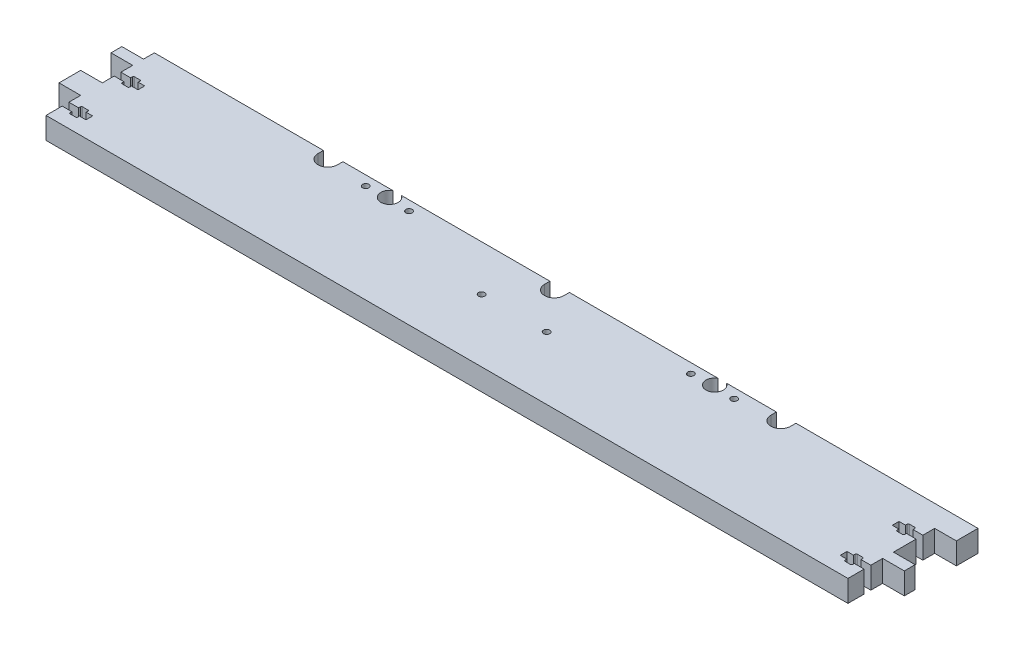
SolidWorks part; units mm, degrees
ref_plane "Front Plane" through (0, 0, 0) normal (0, 0, 1) x (1, 0, 0)
ref_plane "Top Plane" through (0, 0, 0) normal (0, 1, 0) x (1, 0, 0)
ref_plane "Right Plane" through (0, 0, 0) normal (1, 0, 0) x (0, 0, -1)
sketch "Sketch1" plane through (0, 0, 0) normal (0, 1, 0) x (1, 0, 0)
  line L0 (0, 25) -> (0, -25)
  line L1 (-185, 25) -> (0, 25)
  line L2 (-185, 25) -> (-185, -25) construction
  line L3 (-185, -25) -> (0, -25)
  line L4 (-185, -4) -> (-195, -4) construction
  line L5 (-185, 25) -> (0, 0) construction
  line L6 (-185, -25) -> (0, 0) construction
  line L7 (-185, -9) -> (-195, -9)
  line L8 (-195, -9) -> (-195, 1)
  line L9 (-195, 1) -> (-185, 1)
  line L10 (-185, 1) -> (-185, 25)
  line L11 (-185, -9) -> (-185, -25)
  line L47 (0, -25) -> (0, 25) construction
  line L89 (0, -25) -> (0, 25) construction
  point P0 (0, 0)
  dimension "D1" = 185
  dimension "D25" = 25
  dimension "D4" = 50
  dimension "D3" = 21
  dimension "D5" = 10
  dimension "D6" = 10
  dimension "D7" = 5
extrude "MainBody" add sketch "Sketch1" along normal blind 10 contours L3 region at (-93.5428, 0, 0.0428)
sketch "Sketch5" plane through (0, 10, 0) normal (0, 1, 0) x (1, 0, 0)
  line L0 (-185, 8) -> (-174, 8) construction
  line L1 (-185, 1) -> (-185, 25) construction
  line L2 (-185, 9.55) -> (-174, 9.55) construction
  line L3 (-174, 9.55) -> (-174, 6.45) construction
  line L4 (-174, 6.45) -> (-185, 6.45) construction
  line L5 (-185, 9.55) -> (-180.5, 9.55)
  line L6 (-180.5, 9.55) -> (-180.5, 10.35)
  line L7 (-180, 10.85) -> (-177.5, 10.85)
  line L8 (-177, 10.35) -> (-177, 9.55)
  line L9 (-177, 9.55) -> (-174, 9.55)
  line L10 (-174, 9.55) -> (-174, 6.45)
  line L11 (-185, 6.45) -> (-185, 9.55)
  line L12 (-195, -9) -> (-195, 1) construction
  line L13 (-185, 6.45) -> (-174, 6.45) construction
  line L14 (-177, 6.45) -> (-174, 6.45)
  line L15 (-177, 5.65) -> (-177, 6.45)
  line L16 (-180, 5.15) -> (-177.5, 5.15)
  line L17 (-180.5, 6.45) -> (-180.5, 5.65)
  line L18 (-185, 6.45) -> (-180.5, 6.45)
  line L19 (-185, 1) -> (-185, -9) construction
  line L20 (-195, -4) -> (-185, -4) construction
  line L21 (-195, -9) -> (-195, 1) construction
  line L22 (-185, -14.45) -> (-174, -14.45) construction
  line L23 (-174, -14.45) -> (-185, -14.45) construction
  line L24 (-174, -17.55) -> (-174, -14.45) construction
  line L25 (-185, -17.55) -> (-174, -17.55) construction
  line L26 (-185, -16) -> (-174, -16) construction
  line L27 (-185, -14.45) -> (-180.5, -14.45)
  line L28 (-180.5, -14.45) -> (-180.5, -13.65)
  line L29 (-180, -13.15) -> (-177.5, -13.15)
  line L30 (-177, -13.65) -> (-177, -14.45)
  line L31 (-177, -14.45) -> (-174, -14.45)
  line L32 (-185, -14.45) -> (-185, -17.55)
  line L33 (-174, -17.55) -> (-174, -14.45)
  line L34 (-177, -17.55) -> (-174, -17.55)
  line L35 (-177, -18.35) -> (-177, -17.55)
  line L36 (-180, -18.85) -> (-177.5, -18.85)
  line L37 (-180.5, -17.55) -> (-180.5, -18.35)
  line L38 (-185, -17.55) -> (-180.5, -17.55)
  line L39 (-185, 6.45) -> (-174, 6.45) construction
  arc A0 (-177.5, 10.85) -> (-177, 10.35) centre (-177.5, 10.35) cw
  arc A1 (-180.5, 10.35) -> (-180, 10.85) centre (-180, 10.35) cw
  arc A2 (-180.5, 5.65) -> (-180, 5.15) centre (-180, 5.65) ccw
  arc A3 (-177.5, 5.15) -> (-177, 5.65) centre (-177.5, 5.65) ccw
  arc A4 (-177.5, -13.15) -> (-177, -13.65) centre (-177.5, -13.65) cw
  arc A5 (-180.5, -13.65) -> (-180, -13.15) centre (-180, -13.65) cw
  arc A6 (-180.5, -18.35) -> (-180, -18.85) centre (-180, -18.35) ccw
  arc A7 (-177.5, -18.85) -> (-177, -18.35) centre (-177.5, -18.35) ccw
  point P6 (-195, -4)
  point P17 (-177, 10.85)
  point P20 (-180.5, 10.85)
  point P29 (-180.5, 5.15)
  point P30 (-177, 5.15)
  point P61 (-177, -13.15)
  point P62 (-180.5, -13.15)
  point P63 (-180.5, -18.85)
  point P64 (-177, -18.85)
  dimension "D8" = 0.5
  dimension "D1" = 11
  dimension "D2" = 1.55
  dimension "D4" = 3.5
  dimension "D5" = 8
  dimension "D6" = 2.85
  dimension "D7" = 12
extrude "ScrewCutouts" cut sketch "Sketch5" against normal through all
mirror "Mirror1" about plane through (0, 0, 0) normal (1, 0, 0) of "ScrewCutouts", "MainBody"
sketch "Sketch3" plane through (0, 10, 0) normal (0, 1, 0) x (1, 0, 0)
  line L0 (2, 25) -> (2, -25) construction
  line L1 (-185, 25) -> (185, 25) construction
  line L2 (-185, -25) -> (185, -25) construction
  line L3 (-63, 20.5) -> (-83, 20.5) construction
  line L4 (-73, 17.5) -> (-73, 25.5) construction
  line L5 (77, 17.5) -> (77, 25.5) construction
  line L6 (67, 20.5) -> (87, 20.5) construction
  circle A0 centre (-73, 21.5) radius 4
  circle A1 centre (-83, 20.5) radius 1.45
  circle A2 centre (-63, 20.5) radius 1.45
  circle A3 centre (67, 20.5) radius 1.45
  circle A4 centre (87, 20.5) radius 1.45
  circle A5 centre (77, 21.5) radius 4
  dimension "D2" = 8
  dimension "D4" = 2.9
  dimension "D1" = 3.5
  dimension "D5" = 75
  dimension "D6" = 2
  dimension "D3" = 10
  dimension "D7" = 1
extrude "RodCutouts" cut sketch "Sketch3" against normal through all
sketch "Sketch6" plane through (0, 10, 0) normal (0, 1, 0) x (1, 0, 0)
  line L0 (-73, 21.5) -> (77, 21.5) construction
  line L1 (2, 21.5) -> (2, -25) construction
  line L2 (-185, -25) -> (185, -25) construction
  line L3 (17, 4) -> (-13, 4) construction
  line L4 (-71.0635, 25) -> (75.0635, 25) construction
  circle A0 centre (-13, 4) radius 1.45
  circle A1 centre (17, 4) radius 1.45
  point P13 (2, 4)
  dimension "D3" = 21
  dimension "D1" = 2.9
  dimension "D2" = 15
extrude "Cut-Extrude1" cut sketch "Sketch6" against normal through all
sketch "Sketch7" plane through (0, 10, 0) normal (0, 1, 0) x (1, 0, 0)
  line L0 (-73, 21.5) -> (77, 21.5) construction
  line L1 (2, 21.5) -> (2, -25) construction
  line L3 (-102.5, 25) -> (-102.5, 22.5) construction
  line L4 (-185, 25) -> (-74.9365, 25) construction
  line L5 (-98, 25) -> (-98, 22.5)
  line L6 (-107, 25) -> (-107, 22.5)
  line L7 (106.5, 25) -> (106.5, 22.5) construction
  line L8 (102, 25) -> (102, 22.5)
  line L9 (111, 25) -> (111, 22.5)
  line L12 (-185, -25) -> (185, -25) construction
  arc A0 (-98, 25) -> (-107, 25) centre (-102.5, 25) ccw
  arc A1 (-107, 22.5) -> (-98, 22.5) centre (-102.5, 22.5) ccw
  arc A2 (102, 25) -> (111, 25) centre (106.5, 25) cw
  arc A3 (111, 22.5) -> (102, 22.5) centre (106.5, 22.5) cw
  point P12 (-102.5, 23.75)
  point P19 (106.5, 23.75)
  dimension "D1" = 4.5
  dimension "D2" = 2.5
  dimension "D3" = 104.5
extrude "BedAdjustmentScrewCutout" cut sketch "Sketch7" against normal through all
sketch "Sketch8" plane through (0, 10, 0) normal (0, 1, 0) x (1, 0, 0)
  line L0 (88.25, 20.5) -> (89.25, 20.5) construction
  line L1 (88.45, 20.5) -> (88.45, 25) construction
  line L2 (88.25, 20.5) -> (89.25, 21.5)
  line L3 (89.25, 21.5) -> (89.25, 19.5)
  line L4 (88.25, 20.5) -> (89.25, 19.5)
  line L5 (78.9365, 25) -> (102, 25) construction
  circle A1 centre (87, 20.5) radius 1.45 construction
  point P9 (89.25, 20.5)
  dimension "D1" = 1
  dimension "D2" = 1
  dimension "D3" = 0.2
extrude "DirectionKey" [suppressed] cut sketch "Sketch8" against normal through all
sketch "Sketch9" plane through (0, 10, 0) normal (0, 1, 0) x (1, 0, 0)
  line L0 (-13, 4) -> (17, 4) construction
  line L1 (2, 4) -> (2, 25) construction
  line L2 (-71.0635, 25) -> (75.0635, 25) construction
  line L3 (2, 27.5) -> (2, 22.5) construction
  line L4 (6.5, 27.5) -> (6.5, 22.5)
  line L5 (-2.5, 27.5) -> (-2.5, 22.5)
  arc A0 (6.5, 27.5) -> (-2.5, 27.5) centre (2, 27.5) ccw
  arc A1 (-2.5, 22.5) -> (6.5, 22.5) centre (2, 22.5) ccw
  arc A2 (-107, 22.5) -> (-98, 22.5) centre (-102.5, 22.5) ccw construction
  point P10 (2, 25)
  dimension "D2" = 2.5
extrude "Cut-Extrude2" cut sketch "Sketch9" against normal through all
sketch "Sketch10" plane through (0, 10, 0) normal (0, 1, 0) x (1, 0, 0)
  line L0 (195, 1) -> (195, 15) construction
  line L1 (185, 25) -> (195, 25)
  line L2 (185, 25) -> (185, 15)
  line L3 (185, 15) -> (195, 15)
  line L4 (195, 25) -> (195, 15)
  line L5 (195, -9) -> (195, 1) construction
extrude "Boss-Extrude1" add sketch "Sketch10" against normal through all
mirror "Mirror2" about plane through (0, 0, 0) normal (1, 0, 0) of "Boss-Extrude1"
sketch "Sketch11" plane through (0, 10, 0) normal (0, 1, 0) x (1, 0, 0)
  line L0 (-185, 15) -> (-185, 25) construction
  line L1 (-195, 25) -> (-107, 25) construction
  line L3 (-195, 25) -> (-185, 25)
  line L4 (-195, 25) -> (-195, 20)
  line L5 (-195, 20) -> (-185, 20)
  line L6 (-185, 25) -> (-185, 20)
  line L7 (-195, 15) -> (-195, 25) construction
  line L8 (195, -9) -> (195, 1) construction
  line L9 (185, 1) -> (195, 1)
  line L10 (185, 1) -> (185, -4)
  line L11 (185, -4) -> (195, -4)
  line L12 (195, 1) -> (195, -4)
extrude "Cut-Extrude3" cut sketch "Sketch11" against normal through all
equation "\"Y-ROD-SPACING\"=75"
equation "\"Y-BED-OFFSET\"=2"
equation "\"T-SLOT-NUT-FILLET-RADIUS\"=0.5"
equation "\"T-SLOT-SCREW-SHAFT-RADIUS\"=1.55"
equation "\"T-SLOT-SCREW-SHAFT-CUTOUT-LENGTH\"=11"
equation "\"T-SLOT-NUT-DEPTH\"=3.5"
equation "\"T-SLOT-NUT-WIDTH\"=2.85"
equation "\"T-SLOT-NUT-END-DISTANCE\"=8"
equation "\"ACRYLIC-TAB-CUTOUT-SIZE\"=\"ACRYLIC-THICKNESS\"+\"ACRYLIC-TAB-TOLERANCE\"*2"
equation "\"ACRYLIC-M3-HOLE\"=2.9"
equation "\"D1@Sketch5\"=\"T-SLOT-SCREW-SHAFT-CUTOUT-LENGTH\""
equation "\"D2@Sketch5\"=\"T-SLOT-SCREW-SHAFT-RADIUS\""
equation "\"D4@Sketch5\"=\"T-SLOT-NUT-DEPTH\""
equation "\"D5@Sketch5\"=\"T-SLOT-NUT-END-DISTANCE\""
equation "\"D6@Sketch5\"=\"T-SLOT-NUT-WIDTH\""
equation "\"D8@Sketch5\"=\"T-SLOT-NUT-FILLET-RADIUS\""
equation "\"D4@Sketch3\"=\"ACRYLIC-M3-HOLE\""
equation "\"D5@Sketch3\"=\"Y-ROD-SPACING\""
equation "\"D6@Sketch3\"=\"Y-BED-OFFSET\""
equation "\"Y-BED-ROD-INSET\"=3.5"
equation "\"D1@Sketch3\"=\"Y-BED-ROD-INSET\""
equation "\"SMOOTHROD-CAP-SCREW-DISTANCE\"=20"
equation "\"D3@Sketch3\"=\"SMOOTHROD-CAP-SCREW-DISTANCE\"/2"
equation "\"ACRYLIC-TAB-WIDTH\"=\"ACRYLIC-THICKNESS\""
equation "\"FRAME-WIDTH-INNER\"=370"
equation "\"D6@Sketch1\"=\"ACRYLIC-TAB-WIDTH\""
equation "\"D5@Sketch1\"=\"ACRYLIC-TAB-WIDTH\""
equation "\"D1@Sketch1\"=\"FRAME-WIDTH-INNER\"/2"
equation "\"X-ROD-SPACING\"=45"
equation "\"Z-ROD-SPACING\"=17.5"
equation "\"ACRYLIC-THICKNESS\"=10"
equation "\"ACRYLIC-THICKNESS2\"=4.5"
equation "\"NEMA17-HOLE-SPACING\"=31"
equation "\"NEMA17-CENTRAL-CUTOUT\"=22.5"
equation "\"Z-BRACKET-REACH\"=57"
equation "\"TOP-BRACKET-SPACING\"=40"
equation "\"SMOOTHROD-X-LENGTH\"=350"
equation "\"SMOOTHROD-Y-LENGTH\"=350"
equation "\"SMOOTHROD-Z-LENGTH\"=350"
equation "\"SMOOTHROD-TIGHTENING-HEADROOM\"=.25"
equation "\"LEADSCREW-Z-LENGTH\"=300"
equation "\"SCREW-LENGTH-FRAME\"=\"ACRYLIC-THICKNESS\" + 10"
equation "\"SCREW-HEAD-RADIUS\"=6"
equation "\"PRINTED-X-SMOOTHROD-DIAMETER\"=8.8"
equation "\"PRINTED-X-SMOOTHROD-CUTOUT\"=10"
equation "\"PRINTED-X-BASE-HEIGHT\"=10"
equation "\"PRINTED-LM8UU-CUTOUT-SIZE\"=15.5"
equation "\"PRINTED-LM8UU-CUTOUT-LENGTH\"=24.5"
equation "\"PRINTED-X-IDLER-HEIGHT\"=16"
equation "\"PSU-MOUNTING-WIDTH\"=50"
equation "\"PSU-MOUNTING-HEIGHT\"=150"
equation "\"D1@MainBody\"=\"ACRYLIC-THICKNESS\""
equation "\"D7@Sketch1\"=\"ACRYLIC-TAB-WIDTH\"/2"
equation "\"D1@Sketch6\"=\"ACRYLIC-M3-HOLE\""
equation "\"Y-BELT-TO-ROD-DISTANCE\"=20"
equation "\"Y-BED-SCREW-SPACING\"=209"
equation "\"Z-ROD-INSET\"=13.5"
equation "\"SPOOL-HOLDER-ROD-SPACING\"=150"
equation "\"D3@Sketch7\"=\"Y-BED-SCREW-SPACING\"/2"
equation "\"Y-BED-SCREW-CUTOUT-SLOT-HEIGHT\"=2.5"
equation "\"D2@Sketch7\"=\"Y-BED-SCREW-CUTOUT-SLOT-HEIGHT\""
equation "\"ACRYLIC-TAB-TOLERANCE\"=-.05"
equation "\"SCREW-LENGTH-MOTOR\"=\"ACRYLIC-THICKNESS\" + 5"
equation "\"SCREW-LENGTH-EXTRUDER\"=28"
equation "\"PRINTED-M3-HOLE\"=3.5"
equation "\"ACRYLIC-X-CARRIAGE-WIDTH\"=55"
equation "\"ACRYLIC-X-CARRIAGE-HEIGHT\"=75"
equation "\"ACRYLIC-X-CARRIAGE-LM8UU-CUTOUT-WIDTH\"=24.25"
equation "\"ACRYLIC-X-CARRIAGE-LM8UU-CUTOUT-HEIGHT\"=11.0"
equation "\"ACRYLIC-X-CARRIAGE-SCREW-SPACING-X\"=15"
equation "\"ACRYLIC-X-CARRIAGE-SCREW-SPACING-Y\"=33"
equation "\"ACRYLIC-X-CARRIAGE-CENTER-TAB-SPACING\"=14"
equation "\"ACRYLIC-X-CARRIAGE-EXTRUDER-OFFSET\"=26"
equation "\"ACRYLIC-X-CARRIAGE-EXTRUDER-ANGLE\"=90"
equation "\"ACRYLIC-X-CARRIAGE-EXTRUDER-SHELF-DEPTH\"=\"ACRYLIC-X-CARRIAGE-EXTRUDER-OFFSET\" + 28"
equation "\"ACRYLIC-X-CARRIAGE-EXTRUDER-BRACE-SPACING\"=23"
equation "\"ACRYLIC-X-CARRIAGE-EXTRUDER-BRACE-TAB-OFFSET\"=20"
equation "\"ACRYLIC-X-CARRIAGE-EXTRUDER-BRACE-HEIGHT\"=35"
equation "\"ACRYLIC-X-CARRIAGE-EXTRUDER-BRACE-SCREW-SPACING\"=22"
equation "\"ACRYLIC-X-CARRIAGE-DUAL-WIDTH-MULTIPLIER\"=1.65"
equation "\"ACRYLIC-X-CARRIAGE-DUAL-HOTEND-SPACING\"=42"
equation "\"ACRYLIC-X-CARRIAGE-DUAL-WIDTH\"=75"
equation "\"ACRYLIC-X-CARRIAGE-DUAL-HOTEND-SEPARATION\"=36"
equation "\"ACRYLIC-X-CARRIAGE-DUAL-MOUNT-PLATE-DEPTH\"=75"
equation "\"ACRYLIC-X-CARRIAGE-DUAL-MOUNT-BRACE-WIDTH\"=33"
equation "\"ACRYLIC-X-CARRIAGE-DUAL-MOUNT-SCREW-WIDTH\"=40"
equation "\"BLOWER-FAN-WIDTH\"=15"
equation "\"D2@Sketch9\"=\"Y-BED-SCREW-CUTOUT-SLOT-HEIGHT\""
